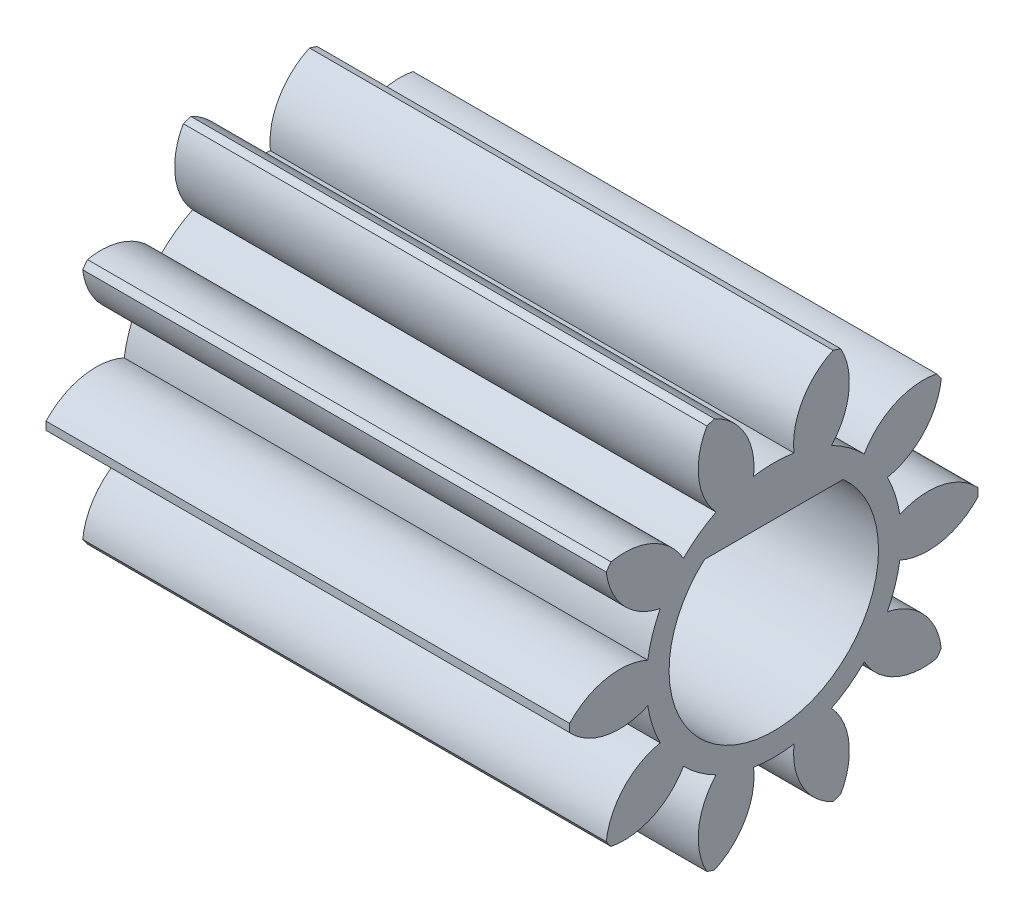
SolidWorks part; units mm, degrees
ref_plane "Plane1" through (0, 0, 0) normal (0, 0, 1) x (1, 0, 0)
ref_plane "Plane2" through (0, 0, 0) normal (0, 1, 0) x (1, 0, 0)
ref_plane "Plane3" through (0, 0, 0) normal (1, 0, 0) x (0, 0, -1)
sketch "HoldingSke" plane through (0, 0, 0) normal (0, 1, 0) x (1, 0, 0)
  line L0 (0, 0) -> (1.5151, -0.2672)
  line L1 (-15, 0) -> (100, 0) construction
  line L2 (0, 0) -> (-2.1039, 2.3779)
  line L3 (0, 0) -> (-11.863, 4.5341)
  line L4 (0, 0) -> (8.5048, 1.4996)
  line L5 (0, 0) -> (-46.8476, -17.4728)
  line L6 (0, 0) -> (-8.2896, -5.593)
  line L7 (-2.1039, 2.3779) -> (8.6586, 51.2059)
  line L8 (-76.2, 54.61) -> (-75.5, 54.61)
  line L9 (-71.009, 38.7566) -> (-53.1078, 45.2721)
  line L10 (-76.2, 71.12) -> (104.1128, 71.12)
  line L11 (0, 0) -> (-10, 0)
  line L12 (-76.2, 101.6) -> (-76.175, 101.6)
  line L13 (24.9733, 27.94) -> (52.9518, 28.4284)
  line L14 (24.9733, 27.94) -> (24.9743, 27.94)
  line L15 (24.9733, 27.94) -> (100.4006, 29.5858)
  line L16 (-63.627, -0.65) -> (-12.827, -0.65)
  circle A0 centre (0, 0) radius 2
  circle A1 centre (0, 0) radius 2.4365
  circle A2 centre (0, 0) radius 37.5
  circle A3 centre (0, 0) radius 2
  dimension "Num_teeth" = 10
  dimension "Pitch_radius" = 180.3128
  dimension "Width" = 10
  dimension "Thickness" = 10
sketch "BasProSke" plane through (0, 0, 0) normal (0, 1, 0) x (1, 0, 0)
  line L0 (-10, 0) -> (60, 0) construction
  line L1 (0, 0) -> (0, 3.9)
  line L2 (0, 0) -> (10, 0)
  line L3 (10, 0) -> (10, 3.9)
  line L4 (10, 3.9) -> (0, 3.9)
  dimension "Thickness" = 10
  dimension "Diameter" = 7.8
revolve "Base-Revolve" add sketch "BasProSke" angle 360 about L0
sketch "TooCutSke" plane through (0, 0, 0) normal (1, 0, 0) x (0, 0, -1)
  line L1 (0, 0) -> (0, 107) construction
  line L2 (0, 0) -> (-0.5521, 3.2028) construction
  line L3 (0, 0) -> (-1.988, 6.1184) construction
  line L4 (-0.5521, 3.2028) -> (-0.994, 3.0592) construction
  arc A0 (0.3857, 2.4058) -> (-0.3857, 2.4058) centre (0, 0) ccw
  arc A1 (1.1674, 3.7478) -> (-1.1674, 3.7478) centre (0, 0) ccw
  circle A2 centre (0, 0) radius 3.25 construction
  circle A3 centre (0, 0) radius 3.054 construction
  arc A4 (-0.3857, 2.4058) -> (-1.1674, 3.7478) centre (-1.6775, 2.5521) ccw
  arc A5 (1.1674, 3.7478) -> (0.3857, 2.4058) centre (1.6775, 2.5521) ccw
extrude "ToothCut" cut sketch "TooCutSke" along normal through all
fillet "Breaks" [suppressed] radius 0.013 tangent propagation no
fillet "RootFillets" [suppressed] radius 0.1635
pattern_circular "TeethCuts" count 10 every 36 about axis through (-10, 0, 0) along (1, 0, 0) of "ToothCut", "RootFillets", "Breaks"
sketch "HubNeaOneSke" plane through (0, 0, 0) normal (-1, 0, 0) x (0, 0, 1)
  circle A0 centre (0, 0) radius 2.4365
  dimension "Diameter" = 4.873
extrude "HubNearOne" [suppressed] add sketch "HubNeaOneSke" along normal blind 40.0001
sketch "HubNeaBotSke" plane through (0, 0, 0) normal (-1, 0, 0) x (0, 0, 1)
  circle A0 centre (0, 0) radius 2.4365
  dimension "Diameter" = 4.873
extrude "HubNearBoth" [suppressed] add sketch "HubNeaBotSke" along normal blind 20
ref_plane "FarPln" through (10, 0, 0) normal (1, 0, 0) x (0, 0, -1)
sketch "HubFarSke" plane through (10, 0, 0) normal (1, 0, 0) x (0, 0, -1)
  circle A0 centre (0, 0) radius 2.4365
  dimension "Diameter" = 4.873
extrude "HubFar" [suppressed] add sketch "HubFarSke" along normal blind 20
sketch "BorSke" plane through (0, 0, 0) normal (1, 0, 0) x (0, 0, -1)
  circle A0 centre (0, 0) radius 2
  dimension "Diameter" = 4
extrude "Bore" cut sketch "BorSke" along normal mid plane 100.0001
sketch "KeySke" plane through (0, 0, 0) normal (1, 0, 0) x (0, 0, -1)
  line L0 (-0.8, 0) -> (-0.8, 2.7)
  line L1 (-0.8, 2.7) -> (0.8, 2.7)
  line L2 (0.8, 2.7) -> (0.8, 0)
  line L3 (0, 0) -> (0, 34) construction
  line L4 (-0.8, 0) -> (0.8, 0)
  dimension "Width" = 1.6
extrude "Keyway" [suppressed] cut sketch "KeySke" along normal mid plane 100.0001
pattern_circular "Keyway2" [suppressed] count 2 every 90 about axis through (-10, 0, 0) along (1, 0, 0) reverse direction yes
sketch "Sketch1" plane through (10, 0, 0) normal (1, 0, 0) x (0, 0, -1)
  line L0 (0, -2) -> (0, 1.5) construction
  line L1 (-1.3229, 1.5) -> (1.3229, 1.5)
  circle A0 centre (0, 0) radius 2 construction
  arc A1 (-1.3229, 1.5) -> (1.3229, 1.5) centre (0, 0) cw
extrude "Boss-Extrude1" add sketch "Sketch1" against normal blind 10
equation "' \"Module@HoldingSke\" = 6.35"
equation "' \"Num_teeth@HoldingSke\" = 12"
equation "' \"Ap@HoldingSke\" =  20"
equation "' \"Ap@HoldingSke\" = 20"
equation "' \"Width@HoldingSke\" = 0.5 * 25.4"
equation "' \"Hub_dia@HoldingSke\"= 1 * 25.4"
equation "' \"Hub_dia@HoldingSke\" = 1 * 25.4"
equation "' \"Overall_len@HoldingSke\" = 1.0 * 25.4"
equation "' \"Bore@HoldingSke\" = 0.75 * 25.4"
equation "' \"T_dim@HoldingSke\" = 0.1 * 25.4"
equation "' \"Width@KeySke\" = 0.25 * 25.4"
equation "' \"Show_teeth@HoldingSke\" = 13"
equation "' \"Backlash@HoldingSke\" = 0.009 * 25.4"
equation "' \"Addendum_fac@HoldingSke\" = 1.0"
equation "' \"Dedendum_fac@HoldingSke\" = 1.25"
equation "' \"Dedendum_add@HoldingSke\" = 0.00005 * 25.4"
equation "' \"Clearance_fac@HoldingSke\" = 0.25"
equation "\"Pitch@HoldingSke\" = 1 / \"Module@HoldingSke\""
equation "\"Overcut_dia@TooCutSke\" = (\"Num_teeth@HoldingSke\" + 2 * \"Addendum_fac@HoldingSke\") / \"Pitch@HoldingSke\" + 0.002 * 25.4"
equation "\"Pitch_dia@TooCutSke\" = \"Num_teeth@HoldingSke\" / \"Pitch@HoldingSke\""
equation "\"Base_dia@TooCutSke\" = \"Num_teeth@HoldingSke\" / \"Pitch@HoldingSke\" * cos((\"Ap@HoldingSke\"  * 3.14159265 / 180))"
equation "\"Root_dia@TooCutSke\" = (\"Num_teeth@HoldingSke\" + 2) / \"Pitch@HoldingSke\" - 2 * (\"Addendum_fac@HoldingSke\" + \"Dedendum_fac@HoldingSke\") / \"Pitch@HoldingSke\" - \"Dedendum_add@HoldingSke\" * 2"
equation "\"Half_ang@TooCutSke\" = 180 / \"Num_teeth@HoldingSke\""
equation "\"Half_CT@TooCutSke\" = \"Num_teeth@HoldingSke\" / \"Pitch@HoldingSke\" * sin((3.14159265 / 2 / \"Num_teeth@HoldingSke\")) / 2 - 7 * \"Backlash@HoldingSke\" / 4"
equation "\"Flank_rad@TooCutSke\" = \"Num_teeth@HoldingSke\" / \"Pitch@HoldingSke\" / 5"
equation "\"Radius@RootFillets\" = \"Clearance_fac@HoldingSke\" / \"Pitch@HoldingSke\" + \"Dedendum_add@HoldingSke\""
equation "\"Break_rad@Breaks\" = 0.02 / \"Pitch@HoldingSke\""
equation "\"Thickness@HoldingSke\" = \"Width@HoldingSke\""
equation "\"OAL@HoldingSke\" = \"Thickness@HoldingSke\""
equation "\"MHD@HoldingSke\" = (\"Num_teeth@HoldingSke\" + 2) / \"Pitch@HoldingSke\" - 2 * (\"Addendum_fac@HoldingSke\" + \"Dedendum_fac@HoldingSke\")  / \"Pitch@HoldingSke\" - \"Dedendum_add@HoldingSke\" * 2"
equation "\"MBD@HoldingSke\" = (\"Num_teeth@HoldingSke\" + 2) / \"Pitch@HoldingSke\" - 2 * (\"Addendum_fac@HoldingSke\" + \"Dedendum_fac@HoldingSke\")  / \"Pitch@HoldingSke\" - \"Dedendum_add@HoldingSke\" * 2 - 0.002 * 25.4"
equation "\"MHD@HoldingSke\" = ((sgn( \"MHD@HoldingSke\" - \"Hub_dia@HoldingSke\" )-1)*( \"MHD@HoldingSke\" - \"Hub_dia@HoldingSke\" ))/-2+ \"Hub_dia@HoldingSke\""
equation "\"MBD@HoldingSke\" = ((sgn( \"MBD@HoldingSke\" - \"Bore@HoldingSke\" )-1)*( \"MBD@HoldingSke\" - \"Bore@HoldingSke\" ))/-2+ \"Bore@HoldingSke\""
equation "\"OAL@HoldingSke\" = ((sgn( \"OAL@HoldingSke\" - \"Overall_len@HoldingSke\" )+1)*( \"OAL@HoldingSke\" - \"Overall_len@HoldingSke\" ))/2 + \"Overall_len@HoldingSke\" + 0.000002 * 25.4"
equation "\"Num_teeth@TeethCuts\" = int( \"Show_teeth@HoldingSke\" ) + 1"
equation "\"Num_teeth@TeethCuts\" = ((sgn( \"Num_teeth@TeethCuts\" - \"Num_teeth@HoldingSke\" )-1)*( \"Num_teeth@TeethCuts\" - \"Num_teeth@HoldingSke\" ))/-2+ \"Num_teeth@HoldingSke\""
equation "\"Num_teeth@TeethCuts\" = ((sgn( \"Num_teeth@TeethCuts\" - 2.0)+1)*( \"Num_teeth@TeethCuts\" - 2.0))/2 +2.0"
equation "\"Angle@TeethCuts\" = 360.0 / \"Num_teeth@HoldingSke\""
equation "\"Diameter@BasProSke\" = (\"Num_teeth@HoldingSke\" + 2 * \"Addendum_fac@HoldingSke\") / \"Pitch@HoldingSke\""
equation "\"Thickness@BasProSke\"  = \"Thickness@HoldingSke\""
equation "' \"Fillet_rad@BasProSke\" =  \"Thickness@HoldingSke\" * 0.05"
equation "' \"Fillet_rad@BasProSke\" = \"Thickness@HoldingSke\" * 0.05"
equation "\"MHD@HoldingSke\" = ((sgn( \"MHD@HoldingSke\" - \"Root_dia@TooCutSke\" )-1)*( \"MHD@HoldingSke\" - \"Root_dia@TooCutSke\" ))/-2+ \"Root_dia@TooCutSke\""
equation "\"Diameter@HubNeaOneSke\" = \"MHD@HoldingSke\""
equation "\"Length@HubNearOne\" = \"OAL@HoldingSke\" - \"Thickness@BasProSke\""
equation "\"Diameter@HubNeaBotSke\" = \"MHD@HoldingSke\""
equation "\"Length@HubNearBoth\" = ( \"OAL@HoldingSke\" - \"Thickness@BasProSke\" ) / 2.0"
equation "\"Thickness@FarPln\" = \"Thickness@BasProSke\""
equation "\"Diameter@HubFarSke\" = \"MHD@HoldingSke\""
equation "\"Length@HubFar\" = ( \"OAL@HoldingSke\" - \"Thickness@BasProSke\" ) / 2.0"
equation "\"Diameter@BorSke\" = \"MBD@HoldingSke\""
equation "\"D1@Bore\" = \"OAL@HoldingSke\" * 2.0"
equation "\"D1@Keyway\" = \"OAL@HoldingSke\" * 2.0"
equation "\"Offset@KeySke\" = \"T_dim@HoldingSke\" + \"MBD@HoldingSke\" / 2.0"
